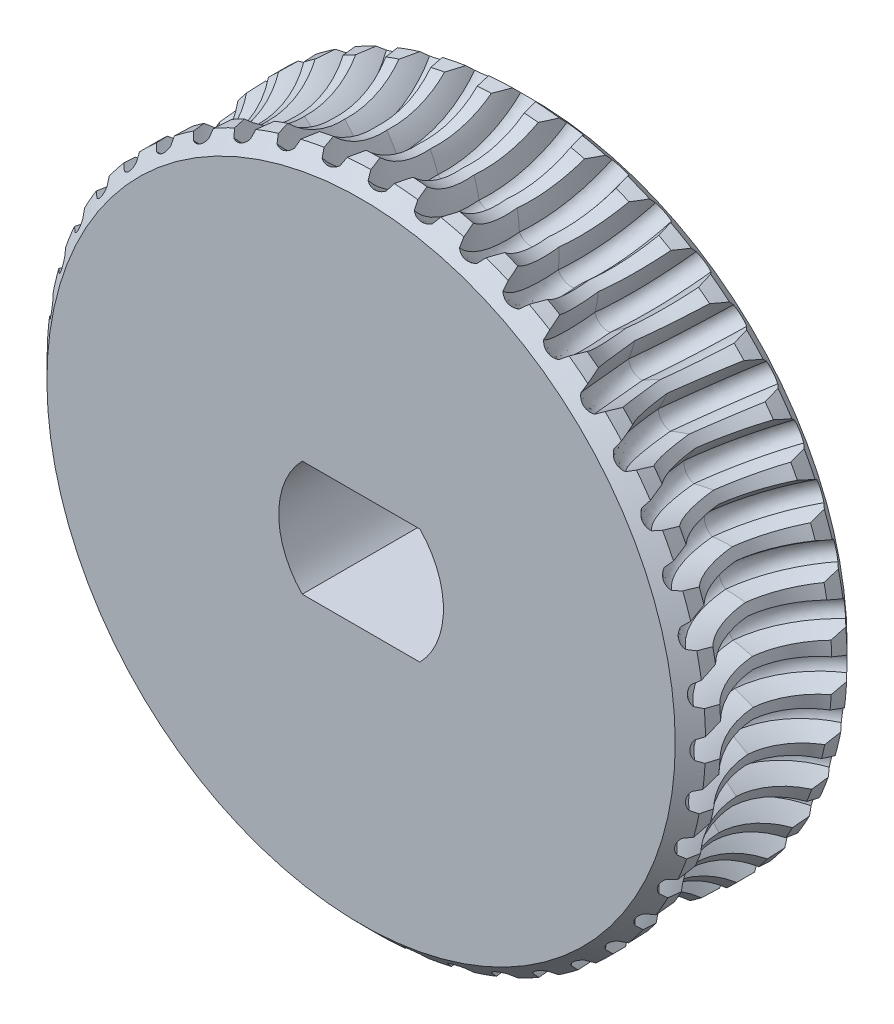
SolidWorks part; units mm, degrees
ref_plane "Front Plane" through (0, 0, 0) normal (0, 0, 1) x (1, 0, 0)
ref_plane "Top Plane" through (0, 0, 0) normal (0, 1, 0) x (1, 0, 0)
ref_plane "Right Plane" through (0, 0, 0) normal (1, 0, 0) x (0, 0, -1)
sketch "Sketch1" plane through (0, 0, 0) normal (0, 0, 1) x (1, 0, 0)
  circle A0 centre (0, 0) radius 43.5
  dimension "D1" = 87
extrude "Boss-Extrude1" add sketch "Sketch1" along normal mid plane 22.7
chamfer "Chamfer1" distance 2 angle 45 2 edges at (43.5, 0, -11.35) (43.5, 0, 11.35)
sketch "Sketch2" plane through (0, 0, 0) normal (1, 0, 0) x (0, 0, -1)
  line L0 (0, -51) -> (0, 0) construction
  line L1 (0, 0) -> (51.6939, 0) construction
  circle A0 centre (0, -51) radius 10.5
  dimension "D1" = 21
  dimension "D2" = 51
revolve "Cut-Revolve2" cut sketch "Sketch2" angle 360 about L1
sketch "Sketch3" plane through (0, 0, 0) normal (1, 0, 0) x (0, 0, -1)
  circle A1 centre (0, -51) radius 10.5
  circle A2 centre (0, -51) radius 10.5
  dimension "D1" = 0
curve "Helix/Spiral1" pitch 6 height 1.5 turns 0.25
sketch "Sketch4" plane through (0, 0, 0) normal (0, 0, 1) x (1, 0, 0)
  line L0 (-3.36, -44.65) -> (3.54, -44.65)
  line L1 (3.54, -44.65) -> (3.54, -42.65)
  line L2 (-3.36, -44.65) -> (-3.36, -42.65)
  line L3 (0, 0) -> (0, -76.0316) construction
  arc A0 (3.54, -42.65) -> (1.1906, -38) centre (18.262, -32.2932) cw
  arc A1 (1.1906, -38) -> (-1.1906, -38) centre (0, -39.35) ccw
  arc A2 (-1.1906, -38) -> (-3.36, -42.65) centre (-18.4208, -32.7925) cw
  circle A3 centre (0, 0) radius 43.5 construction
  dimension "D2" = 1.8
  dimension "D6" = 18
  dimension "D7" = 18
  dimension "D1" = 6.9
  dimension "D3" = 4.65
  dimension "D4" = 4.65
  dimension "D5" = 3.54
  dimension "D8" = 1.35
  dimension "D9" = 38
  dimension "D10" = 2
sweep "Cut-Sweep1" cut profiles "Sketch4" path "Helix/Spiral1"
mirror "Mirror1" about plane through (0, 0, 0) normal (0, 0, 1) of "Cut-Sweep1"
pattern_circular "CirPattern1" count 44 over 360 about axis through (0, 0, 7.3485) along (0, 0, -1) of "Mirror1", "Cut-Sweep1", "Cut-Revolve2"
scale "Escala2" bodies to scale 105 scale about centroid uniform scaling yes scale factor 0.2298
sketch "Esboço1" plane through (0, 0, 2.6082) normal (0, 0, 1) x (1, 0, 0)
  line L0 (0, 1.75) -> (0, -1.75) construction
  line L1 (-1.7854, 1.75) -> (1.7854, 1.75)
  line L2 (-1.7854, -1.75) -> (1.7854, -1.75)
  arc A0 (1.7854, -1.75) -> (1.7854, 1.75) centre (0, 0) ccw
  arc A1 (-1.7854, 1.75) -> (-1.7854, -1.75) centre (0, 0) ccw
  point P6 (0, 0)
  point P9 (0, 1.75)
  point P12 (0, -1.75)
  dimension "D1" = 2.5
  dimension "D2" = 3.5
extrude "Corte-extrusão1" cut sketch "Esboço1" against normal mid plane 70
